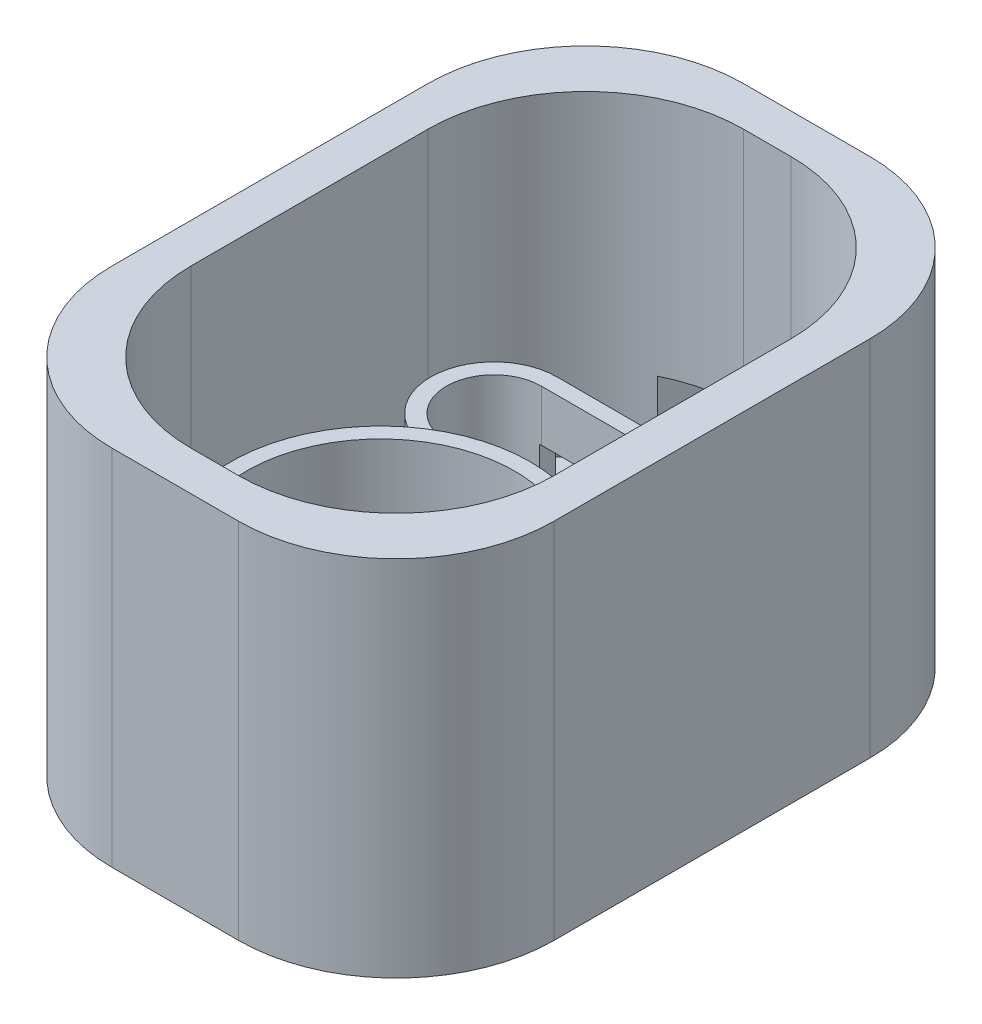
SolidWorks part; units mm, degrees
ref_plane "Front Plane" through (0, 0, 0) normal (0, 0, 1) x (1, 0, 0)
ref_plane "Top Plane" through (0, 0, 0) normal (0, 1, 0) x (1, 0, 0)
ref_plane "Right Plane" through (0, 0, 0) normal (1, 0, 0) x (0, 0, -1)
sketch "Sketch1" plane through (0, 0, 0) normal (0, 1, 0) x (1, 0, 0)
  line L0 (0, 0) -> (0, -32.988) construction
  line L9 (14, -13) -> (-14, -13)
  line L10 (14, -13) -> (14, 27)
  line L11 (14, 27) -> (-14, 27)
  line L12 (-14, -13) -> (-14, 27)
  line L13 (14, -13) -> (-14, 27) construction
  line L14 (14, 27) -> (-14, -13) construction
  line L16 (-11.5, 24.5) -> (11.5, 24.5)
  line L17 (-11.5, 24.5) -> (-11.5, -10.5)
  line L18 (-11.5, -10.5) -> (11.5, -10.5)
  line L19 (11.5, 24.5) -> (11.5, -10.5)
  line L20 (-11.5, 24.5) -> (11.5, -10.5) construction
  line L21 (-11.5, -10.5) -> (11.5, 24.5) construction
  circle A0 centre (0, 0) radius 8.5
  circle A1 centre (0, 0) radius 9.5
  point P10 (0, 7)
  dimension "D1" = 17
  dimension "D2" = 19
  dimension "D3" = 40
  dimension "D4" = 28
  dimension "D5" = 13
  dimension "D6" = 2.5
  dimension "D7" = 2.5
extrude "Boss-Extrude4" add sketch "Sketch1" along normal blind 10 contours L12 L9 L10 L11 L16 L19 L18 L17 | A1 A0 region at (0, 0, 12.5117) region at (-9.2313, 0, 0)
extrude "Boss-Extrude5" add sketch "Sketch1<5>" along normal blind 20 contours L12 L9 L10 L11 L16 L19 L18 L17 region at (0, 0, 12.5117)
sketch "Sketch1<5>" plane through (0, 0, 0) normal (0, 1, 0) x (1, 0, 0) same geometry as "Sketch1"
sketch "Sketch3" plane through (0, 0, 0) normal (0, -1, 0) x (1, 0, 0)
  line L1 (-14, 13) -> (14, 13)
  line L2 (-14, 13) -> (-14, -27)
  line L3 (-14, -27) -> (14, -27)
  line L4 (14, 13) -> (14, -27)
extrude "Boss-Extrude6" add sketch "Sketch3" along normal blind 3
sketch "Sketch4" plane through (0, 0, 0) normal (0, 1, 0) x (1, 0, 0)
  line L0 (-5.816, 13) -> (5.5762, 13) construction
  line L1 (-5.816, 16) -> (5.5762, 16)
  line L2 (-5.816, 10) -> (5.5762, 10)
  line L3 (-5.816, 13) -> (5.5762, 13) construction
  line L4 (-5.816, 17) -> (5.5762, 17)
  line L5 (-5.816, 9) -> (5.5762, 9)
  arc A0 (-5.816, 16) -> (-5.816, 10) centre (-5.816, 13) ccw
  arc A1 (5.5762, 10) -> (5.5762, 16) centre (5.5762, 13) ccw
  arc A3 (-5.816, 17) -> (-5.816, 9) centre (-5.816, 13) ccw
  arc A4 (5.5762, 9) -> (5.5762, 17) centre (5.5762, 13) ccw
  point P2 (-0.1199, 13)
  point P11 (-0.1199, 13)
  dimension "D2" = 1
  dimension "D1" = 9
  dimension "D3" = 6
extrude "Boss-Extrude9" add sketch "Sketch4" along normal blind 8 separate body
sketch "Sketch6" plane through (0, 0, -24.5) normal (0, 0, 1) x (1, 0, 0)
  line L1 (2.0762, 4.7579) -> (5.5762, 4.7579)
  line L2 (2.0762, 4.7579) -> (2.0762, 1.2579)
  line L3 (2.0762, 1.2579) -> (5.5762, 1.2579)
  line L4 (5.5762, 4.7579) -> (5.5762, 1.2579)
  line L5 (1.5762, 4.7579) -> (1.5762, 1.2579)
  line L6 (-1.9238, 4.7579) -> (-1.9238, 1.2579)
  line L7 (-1.9238, 4.7579) -> (1.5762, 4.7579)
  line L8 (-1.9238, 1.2579) -> (1.5762, 1.2579)
  line L9 (-2.4238, 4.7579) -> (-2.4238, 1.2579)
  line L10 (-5.9238, 4.7579) -> (-5.9238, 1.2579)
  line L11 (-5.9238, 4.7579) -> (-2.4238, 4.7579)
  line L12 (-5.9238, 1.2579) -> (-2.4238, 1.2579)
  line L13 (5.5762, 8) -> (5.5762, 0) construction
  dimension "D1" = 3.5
  dimension "D2" = 3.5
  dimension "D4" = 3
extrude "Cut-Extrude2" cut sketch "Sketch6" against normal blind 8 and the other way blind 11
fillet "Fillet1" radius 10 8 edges at (-11.5, 10, 10.5) (11.5, 10, 10.5) (11.5, 10, -24.5) (-11.5, 10, -24.5) (-14, 8.5, -27) (14, 8.5, -27) (14, 8.5, 13) (-14, 8.5, 13)
